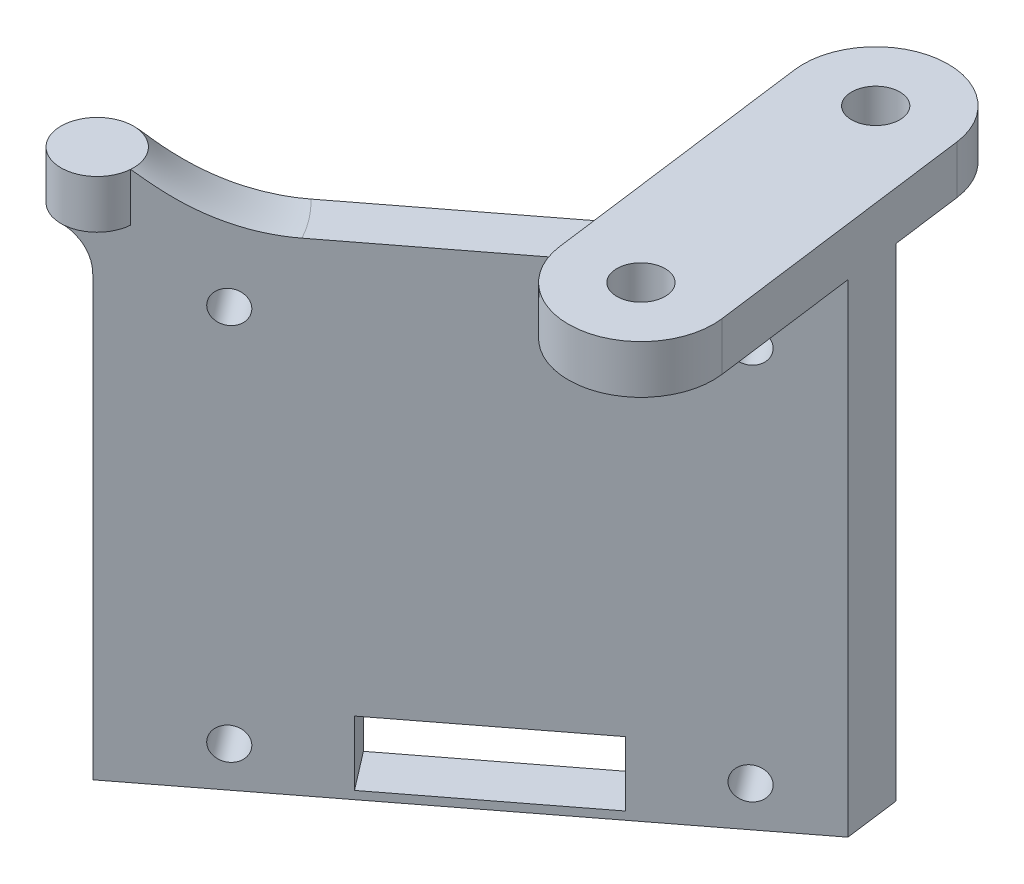
SolidWorks part; units mm, degrees
ref_plane "前基準面" through (0, 0, 0) normal (0, 0, 1) x (1, 0, 0)
ref_plane "上基準面" through (0, 0, 0) normal (0, 1, 0) x (1, 0, 0)
ref_plane "右基準面" through (0, 0, 0) normal (1, 0, 0) x (0, 0, -1)
surface "曲面-偏移1" parameters "D1"=0
sketch "草圖1" plane through (0, 131.6419, 0) normal (0, -1, 0) x (1, 0, 0)
  line L0 (-107.7079, -74.9153) -> (-109.9197, -91.7115) construction
  line L1 (-107.7079, -74.9153) -> (-109.9197, -91.7115) construction
  line L2 (-103.2464, -75.5028) -> (-105.4582, -92.299)
  line L3 (-112.1694, -74.3278) -> (-114.3812, -91.124)
  circle A0 centre (-109.9197, -91.7115) radius 1.5 construction
  circle A1 centre (-107.7079, -74.9153) radius 1.5 construction
  arc A2 (-103.2464, -75.5028) -> (-112.1694, -74.3278) centre (-107.7079, -74.9153) ccw
  arc A3 (-114.3812, -91.124) -> (-105.4582, -92.299) centre (-109.9197, -91.7115) ccw
  circle A4 centre (-109.9197, -91.7115) radius 1.5
  circle A5 centre (-107.7079, -74.9153) radius 1.5
  point P2 (-108.8138, -83.3134)
  dimension "D1" = 4.5
extrude "填料-伸長1" add sketch "草圖1" along normal blind 3
sketch "草圖3" plane through (0, 128.6419, 0) normal (0, -1, 0) x (1, 0, 0)
  line L0 (-107.7079, -74.9153) -> (-109.9197, -91.7115) construction
  line L1 (-109.0058, -84.7714) -> (-132.8058, -66.5079)
  line L2 (-132.8058, -66.5079) -> (-130.9795, -64.1279)
  line L3 (-130.9795, -64.1279) -> (-108.5535, -81.337)
  line L4 (-108.5535, -81.337) -> (-109.0058, -84.7714) construction
  line L5 (-108.5535, -81.337) -> (-110.3799, -83.717) construction
  line L6 (-108.5535, -81.337) -> (-104.4312, -84.5003)
  line L7 (-110.3799, -83.717) -> (-104.8835, -87.9348)
  line L9 (-104.8835, -87.9348) -> (-104.4312, -84.5003)
  line L10 (-105.4582, -92.299) -> (-103.2464, -75.5028) construction
  line M12 (-112.1694, -74.3278) -> (-114.3812, -91.124)
  line M14 (-105.4582, -92.299) -> (-103.2464, -75.5028)
  dimension "D1" = 120
  dimension "D2" = 3
  dimension "D3" = 7
  dimension "D4" = 30
extrude "填料-伸長2" add sketch "草圖3" along normal blind 30 contours L1 L7 L6 L3 M14 M12 | L3 L2 L1 M12
sketch "草圖4" plane through (0, 128.6419, 0) normal (0, 1, 0) x (1, 0, 0)
  line L0 (-132.8058, 66.5079) -> (-130.9795, 64.1279) construction
  circle A0 centre (-131.8927, 65.3179) radius 2.25
  dimension "D1" = 4.5
extrude "填料-伸長3" add sketch "草圖4" along normal blind 3
fillet "圓角1" radius 10 1 edges at (-130.1077, 128.6419, -66.6876)
fillet "圓角3" radius 3 1 edges at (-131.8927, 128.6419, -65.3179)
fillet "圓角5" radius 3 1 edges at (-131.4754, 130.1419, -67.5288)
sketch "草圖5" plane through (-81.3417, 0, -106.0001) normal (-0.6088, 0, -0.7933) x (-0.7933, 0, 0.6088)
  line L1 (41.2725, 99.1419) -> (41.2725, 103.1419)
  line L2 (41.2725, 103.1419) -> (53.2725, 103.1419)
  line L3 (53.2725, 103.1419) -> (53.2725, 99.1419)
  line L4 (53.2725, 99.1419) -> (41.2725, 99.1419)
  line L5 (29.6744, 98.6419) -> (64.8706, 98.6419) construction
  line L6 (35.7225, 101.1419) -> (58.8225, 101.1419) construction
  line L7 (58.8225, 101.1419) -> (58.8225, 124.6419) construction
  line L8 (47.2725, 101.1419) -> (47.2725, 113.6508) construction
  circle A0 centre (35.7225, 101.1419) radius 1
  circle A1 centre (58.8225, 101.1419) radius 1
  circle A2 centre (58.8225, 124.6419) radius 1
  circle A3 centre (35.7225, 124.6419) radius 1
  point P0 (29.5824, 102.8185)
  point P5 (47.2725, 98.6419)
  point P10 (47.2725, 101.1419)
  point P11 (47.2725, 99.1419)
  point P14 (53.2725, 101.1419)
  dimension "D4" = 2
  dimension "D5" = 2
  dimension "D8" = 2
  dimension "D1" = 12
  dimension "D2" = 4
  dimension "D3" = 23.1
  dimension "D6" = 0.5
  dimension "D7" = 23.5
extrude "除料-伸長1" cut sketch "草圖5" against normal blind 3
